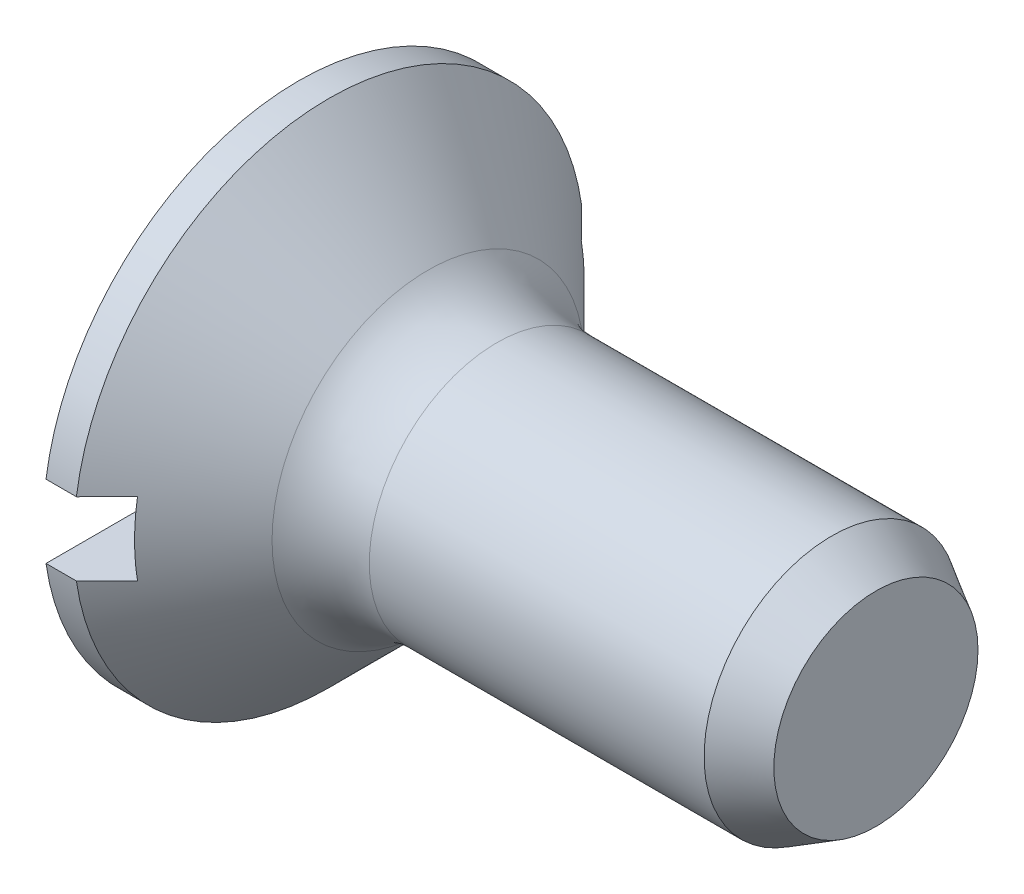
SolidWorks part; units mm, degrees
ref_plane "Front" through (0, 0, 0) normal (0, 0, 1) x (1, 0, 0)
ref_plane "Top" through (0, 0, 0) normal (0, 1, 0) x (1, 0, 0)
ref_plane "Right" through (0, 0, 0) normal (1, 0, 0) x (0, 0, -1)
sketch "Sketch1" plane through (0, 0, 0) normal (0, 0, 1) x (1, 0, 0)
  line L0 (0, 4.2) -> (0.5, 4.2)
  line L1 (0.5, 4.2) -> (2.6, 2.1)
  line L2 (2.6, 2.1) -> (9.5, 2.1)
  line L3 (9.5, 2.1) -> (9.5, 0)
  line L4 (9.5, 0) -> (0, 0)
  line L5 (0, 0) -> (0, 4.2)
  line L6 (6.6207, 0) -> (-0.9387, 0) construction
  dimension "D1" = 45
  dimension "k" = 2.6
revolve "Revolve1" add sketch "Sketch1" angle 360 about L6
cosmetic thread "ThreadCosmetic" [suppressed] parameters "D2"=3.1
sketch "Sketch2" plane through (0, 0, 0) normal (0, 0, 1) x (1, 0, 0)
  line L0 (0, 4.2) -> (0, -4.2) construction
  line L1 (0, 0.6) -> (1, 0.6)
  line L2 (0, 0.6) -> (0, -0.6)
  line L3 (0, -0.6) -> (1, -0.6)
  line L4 (1, 0.6) -> (1, -0.6)
  dimension "n" = 1.2
  dimension "t" = 1
extrude "Cut-Extrude1" cut sketch "Sketch2" against normal through all and the other way through all
chamfer "Chamfer1" distance 0.42 angle 60 1 edges at (9.5, 0, -2.1) first distance on face at (9.5, 0, -2.1)
sketch "Sketch4" plane through (0, 0, 0) normal (0, 0, 1) x (1, 0, 0)
  line L0 (3.8225, 1.55) -> (3.0575, 1.55)
  line L1 (3.0575, 1.55) -> (2.74, 2.1)
  line L2 (3.8225, 1.55) -> (4.14, 2.1)
  line L3 (2.74, 2.1) -> (2.74, 2.35)
  line L4 (4.14, 2.1) -> (4.14, 2.35)
  line L5 (2.74, 2.35) -> (4.14, 2.35)
  line L6 (3.44, 1.55) -> (3.44, 0) construction
  line L7 (0, 0) -> (7.3035, 0) construction
  line L9 (8.7725, 2.1) -> (2.6, 2.1) construction
  line L12 (2.6, 2.1) -> (2.6, -2.1) construction
  dimension "D2" = 60
  dimension "D3" = 0.25
  dimension "minordia" = 3.1
  dimension "threadstart" = 0.84
revolve "ThreadSchematic" [suppressed] cut sketch "Sketch4" angle 360 about L7
pattern_linear "ThdSchPat" [suppressed] count 5 spacing 1.4 along (1, 0, 0) of bodies 137
sketch "Sketch3" plane through (0, 0, 0) normal (0, 0, 1) x (1, 0, 0)
  line L0 (2.6, 2.1) -> (9.5, 2.1) construction
  line L2 (5.8, 2.1) -> (6.725, 2.1) construction
  line L3 (9.5, 2.1) -> (9.5, 0) construction
  line L4 (6.725, 2.1) -> (9.5, 0)
  line L5 (2.9, 0) -> (5.4301, 0) construction
  line L6 (9.5, 0) -> (9.7, 0)
  line L7 (9.7, 0) -> (9.7, 2.1)
  line L8 (9.7, 2.1) -> (9.5, 2.1)
  line L9 (6.725, 2.1) -> (9.5, 2.1)
  dimension "D1" = 0.925
revolve "EndCone" [suppressed] cut sketch "Sketch3" angle 360 about L5
fillet "Fillet1" radius 1.6 1 edges at (2.6, 0, -2.1)
equation "\"minordia@Sketch4\" = \"D2@ThreadCosmetic\""
equation "\"D1@Chamfer1\" = \"d@Sketch1\" / 10"
equation "\"D1@Sketch3\" = \"y@Sketch3\" / 4"
equation "\"threadstart@Sketch4\" = \"advance@Sketch4\"*0.6"
equation "\"D1@ThdSchPat\" = int(((\"l@Sketch1\"-\"k@Sketch1\")/\"advance@Sketch4\") + 0.999)"
equation "\"D3@ThdSchPat\" =\"advance@Sketch4\""
